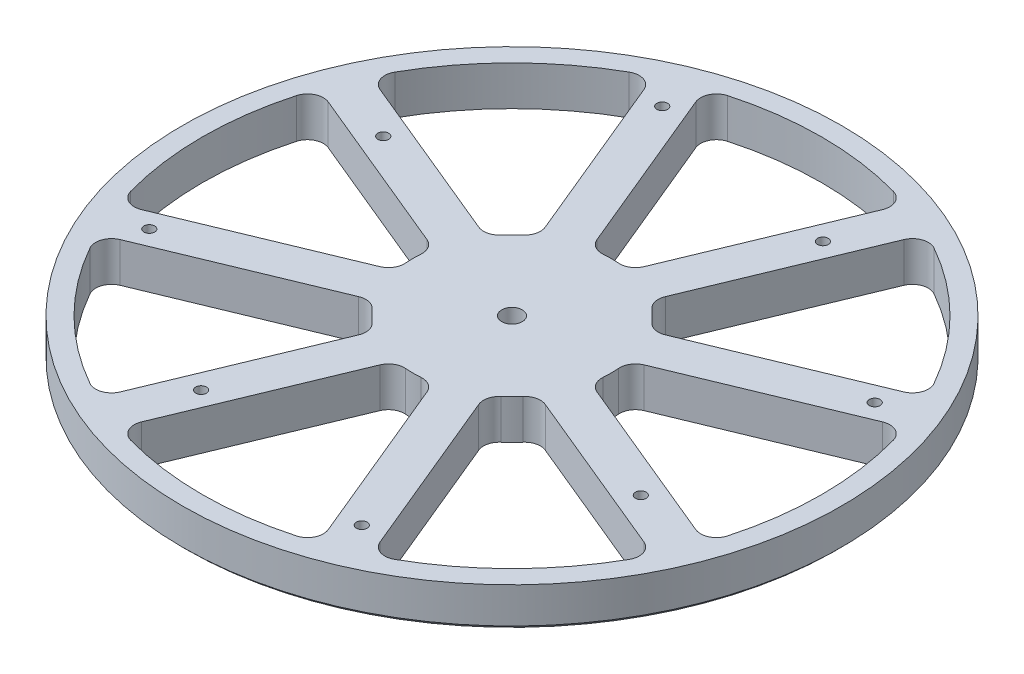
SolidWorks part; units mm, degrees
ref_plane "Front Plane" through (0, 0, 0) normal (0, 0, 1) x (1, 0, 0)
ref_plane "Top Plane" through (0, 0, 0) normal (0, 1, 0) x (1, 0, 0)
ref_plane "Right Plane" through (0, 0, 0) normal (1, 0, 0) x (0, 0, -1)
sketch "Sketch2" plane through (0, 0, 0) normal (1, 0, 0) x (0, 0, -1)
  line L0 (0, 0) -> (-83.0999, 0)
  line L1 (-83.0999, 0) -> (-83.0999, 10)
  line L2 (-83.0999, 10) -> (0, 10)
  line L5 (0, 10) -> (0, 0)
  dimension "D1" = 83.0999
  dimension "D2" = 10
ref_axis "Axis1" through (0, -0.5, 0) along (0, 1, 0)
revolve "Revolve1" add sketch "Sketch2" angle 360 about axis through (0, -0.5, 0) along (0, 1, 0)
hole_wizard "#6-32 Tapped Hole1" positions "Sketch6" profile "Sketch7" tap size "#6-32" standard "ANSI Inch" end condition through all
sketch "Sketch6" plane through (0, 10, 0) normal (0, 1, 0) x (1, 0, 0)
  line L0 (0, 0) -> (-53.438, 129.0108) construction
  line L2 (0, 0) -> (0, 109.0908) construction
  line L3 (0, 0) -> (-76.7743, 31.801) construction
  circle A0 centre (0, 0) radius 83.0999 construction
  point P0 (-26.7878, 64.6716)
  point P18 (-55.4328, 22.961)
  dimension "D1" = 22.5
  dimension "D2" = 70
  dimension "D3" = 45
  dimension "D4" = 60
sketch "Sketch7" plane through (-26.7878, 10, -64.6716) normal (1, 0, 0) x (0, 0, 1)
  line L0 (0, 0) -> (0, 10)
  line L1 (0, 10) -> (1.3525, 10)
  line L2 (1.3525, 10) -> (1.3525, 0)
  line L5 (1.3525, 0) -> (0, 0)
  line L11 (0, -6.35) -> (0, 107.95) construction
  dimension "Thread Major Dia." = 2.7051
  dimension "Thru Tap Drill Depth" = 10
pattern_circular "CirPattern3" count 4 over 360 about axis through (0, -0.5, 0) along (0, 1, 0) of "#6-32 Tapped Hole1"
sketch "Sketch8" plane through (0, 10, 0) normal (0, 1, 0) x (1, 0, 0)
  line L4 (0, 0) -> (0, 93.9995) construction
  line L5 (0, 0) -> (113.8372, 0) construction
  line L6 (-4.7544, 24.5438) -> (-25.2068, 73.9203)
  line L7 (4.7544, 24.5438) -> (25.2068, 73.9203)
  line L8 (0, 0) -> (-26.7878, 64.6716) construction
  arc A0 (-4.7544, 24.5438) -> (4.7544, 24.5438) centre (0, 0) cw
  arc A1 (-25.2068, 73.9203) -> (25.2068, 73.9203) centre (0, 0) cw
  circle A2 centre (0, 0) radius 83.0999 construction
  dimension "D1" = 25
  dimension "D2" = 5
  dimension "D3" = 5
extrude "Cut-Extrude1" cut sketch "Sketch8" against normal through all
fillet "Fillet1" radius 4 4 edges at (4.7544, 5, -24.5438) (25.2068, 5, -73.9203) (-4.7544, 5, -24.5438) (-25.2068, 5, -73.9203)
pattern_circular "CirPattern4" count 8 over 360 about axis through (0, -0.5, 0) along (0, 1, 0) of "Cut-Extrude1", "Fillet1"
chamfer "Chamfer2" distance 1 angle 45 1 edges at (0, 0, -83.0999)
hole_wizard "#6 (0.204) Diameter Hole2" positions "Sketch9" profile "Sketch11" hole size "#6" standard "ANSI Inch" end condition through all
sketch "Sketch9" plane through (0, 0, 0) normal (0, -1, 0) x (-1, 0, 0)
  point P0 (0, 0)
sketch "Sketch11" plane through (0, 0, 0) normal (1, 0, 0) x (0, 0, -1)
  line L0 (0, 0) -> (0, 10)
  line L1 (0, 10) -> (2.5908, 10)
  line L2 (2.5908, 10) -> (2.5908, 0)
  line L5 (2.5908, 0) -> (0, 0)
  line L11 (0, -6.35) -> (0, 107.95) construction
  dimension "Thru Hole Dia." = 5.1816
  dimension "Thru Hole Depth" = 10
equation "\"TubeDiameter\" = 6.5433in"
equation "\"D1@Sketch2\"=\"TubeDiameter\"/2"
